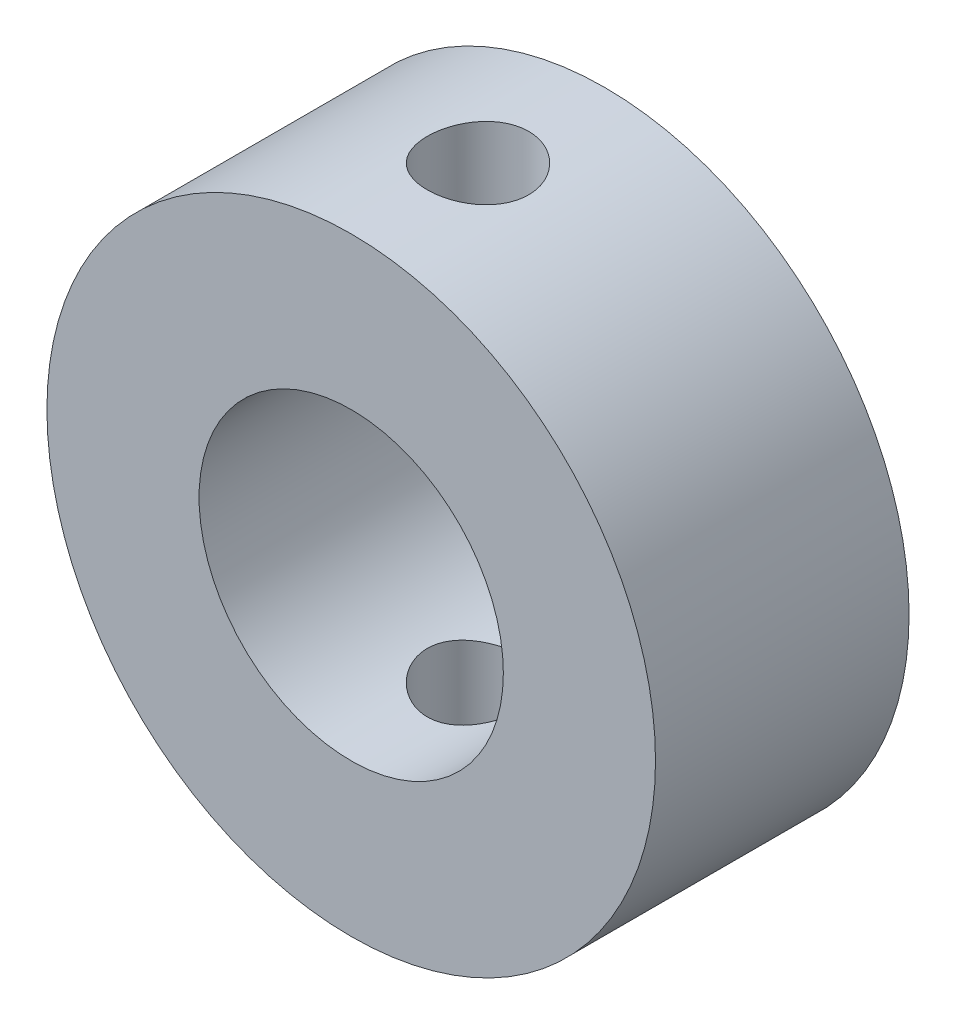
SolidWorks part; units mm, degrees
material "3.3547 (EN-AW 5083)"
ref_plane "Ebene vorne" through (0, 0, 0) normal (0, 0, 1) x (1, 0, 0)
ref_plane "Ebene oben" through (0, 0, 0) normal (0, 1, 0) x (1, 0, 0)
ref_plane "Ebene rechts" through (0, 0, 0) normal (1, 0, 0) x (0, 0, -1)
sketch "Skizze1" plane through (0, 0, 0) normal (0, 0, 1) x (1, 0, 0)
  circle A0 centre (0, 0) radius 3
  circle A1 centre (0, 0) radius 6
extrude "Aufsatz-Linear austragen1" add sketch "Skizze1" along normal blind 5
sketch "Skizze2" plane through (0, 0, 0) normal (0, 1, 0) x (1, 0, 0)
  circle A0 centre (0, -2.5) radius 1
extrude "Schnitt-Linear austragen1" cut sketch "Skizze2" against normal blind 10 and the other way blind 10
